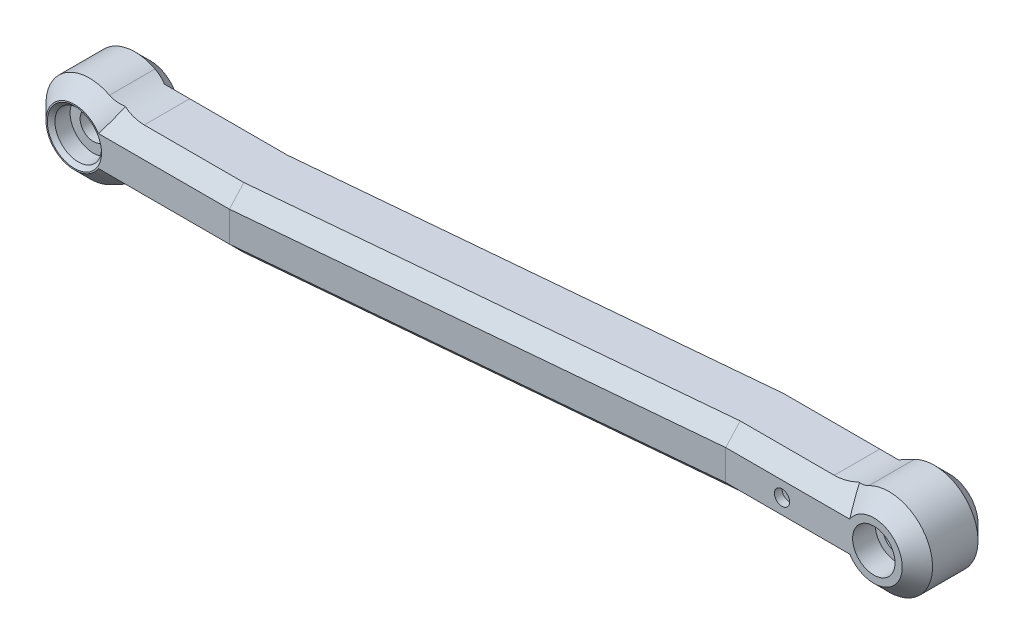
SolidWorks part; units mm, degrees
ref_plane "Plan de face" through (0, 0, 0) normal (0, 0, 1) x (1, 0, 0)
ref_plane "Plan de dessus" through (0, 0, 0) normal (0, 1, 0) x (1, 0, 0)
ref_plane "Plan de droite" through (0, 0, 0) normal (1, 0, 0) x (0, 0, -1)
sketch "Esquisse1" plane through (0, 0, 0) normal (0, 0, 1) x (1, 0, 0)
  line L0 (0, 0) -> (100, 0) construction
  line L1 (4.1307, 4) -> (95.8693, 4)
  line L2 (4.1307, -4) -> (95.8693, -4)
  circle A0 centre (0, 0) radius 1.75
  circle A2 centre (0, 0) radius 5.75
  circle A3 centre (100, 0) radius 1.75
  circle A4 centre (100, 0) radius 5.75
  dimension "D1" = 3.5
  dimension "D3" = 8
  dimension "D4" = 100
  dimension "D2" = 4
extrude "Boss.-Extru.1" add sketch "Esquisse1" along normal blind 20 contours A2 L0 A4 L1 | L0 A2 L2 A4 | A0 | A3 | A2 | A4 region at (50, 2.0116, 0) region at (50, -2.0116, 0) region at (-1.7005, 0, 0) region at (100, 1.7005, 0)
sketch "Esquisse3" plane through (0, -4, 0) normal (0, -1, 0) x (1, 0, 0)
  line L0 (50, 0) -> (50, -61.5446) construction
  line L1 (4.1307, 0) -> (95.8693, 0) construction
  line L2 (95.8693, 0) -> (80, 0)
  line L3 (80, 0) -> (20, 5.5)
  line L4 (20, 5.5) -> (-24.2955, 5.5)
  line L5 (-24.2955, 5.5) -> (-24.2955, -17.5034)
  line L6 (-24.2955, -17.5034) -> (80, -17.5034)
  line L7 (80, -17.5034) -> (80, 0)
  line L8 (122.5802, 10) -> (80.4574, 10)
  line L9 (80.4574, 10) -> (20.4574, 15.5)
  line L10 (20.4574, 15.5) -> (-24.2955, 15.5)
  line L11 (95.8693, 10) -> (80.4574, 10) construction
  line L12 (122.5802, 10) -> (122.5802, 29.3131)
  line L13 (122.5802, 29.3131) -> (-24.2955, 29.3131)
  line L14 (-24.2955, 29.3131) -> (-24.2955, 15.5)
  point P10 (50, 2.75)
  line M3 (4.1307, 0) -> (95.8693, 0)
  line M6 (4.1307, 20) -> (4.1307, 0)
  dimension "D1" = 5.5
  dimension "D2" = 30
  dimension "D3" = 10
extrude "Enlèv. mat.-Extru.1" cut sketch "Esquisse3" against normal through all both and the other way through all contours L0 L4 L5 L6 M3 M6 | L3 L4 M6 M3 | L0 L6 L7 M3 | L10 L14 L13 L12 L8 L9 region at (30.3355, -4, 2.1505) region at (24.8597, -4, -7.8444)
chamfer "Chanfrein1" distance 2 angle 45 16 edges at (-5.75, 0, 5.5) (12.0653, 4, 5.5) (12.0653, -4, 5.5) (50, -4, 2.75) (50, 4, 2.75) (87.9347, 4, 0) (105.75, 0, 0) (87.9347, -4, 0) (-5.75, 0, 15.5) (12.294, 4, 15.5) (12.294, -4, 15.5) (50.4574, -4, 12.75) (88.1633, -4, 10) (105.75, 0, 10) (50.4574, 4, 12.75) (88.1633, 4, 10)
fillet "Congé1" radius 10 4 edges at (4.1307, -4, 10.5) (4.1307, 4, 10.5) (95.8693, 4, 5) (95.8693, -4, 5)
sketch "Esquisse4" plane through (0, 0, 15.5) normal (0, 0, 1) x (1, 0, 0)
  circle A0 centre (0, 0) radius 3.075
  dimension "D1" = 6.15
extrude "Enlèv. mat.-Extru.2" cut sketch "Esquisse4" against normal blind 2.5
ref_plane "Plan1" through (0, 0, 10.5) normal (0, 0, -1) x (-1, 0, 0)
mirror "Symétrie1" about plane through (0, 0, 10.5) normal (0, 0, -1) of "Enlèv. mat.-Extru.2"
sketch "Esquisse5" plane through (0, 0, 0) normal (0, 0, -1) x (-1, 0, 0)
  circle A0 centre (-100, 0) radius 3.075
  dimension "D1" = 6.15
extrude "Enlèv. mat.-Extru.3" cut sketch "Esquisse5" against normal blind 3.2
chamfer "Chanfrein2" distance 0.5 angle 45 5 edges at (3.075, 0, 15.5) (3.075, 0, 5.5) (-1.75, 0, 8) (98.25, 0, 3.2) (96.925, 0, 0)
sketch "Esquisse6" plane through (0, 0, 10) normal (0, 0, 1) x (1, 0, 0)
  circle A0 centre (100, 0) radius 2.8
  dimension "D1" = 5.6
extrude "Enlèv. mat.-Extru.4" cut sketch "Esquisse6" against normal blind 3
sketch "Esquisse7" plane through (0, 0, 10) normal (0, 0, 1) x (1, 0, 0)
  circle A0 centre (87.8842, 0) radius 1
  dimension "D1" = 2
extrude "Enlèv. mat.-Extru.5" cut sketch "Esquisse7" against normal blind 1
